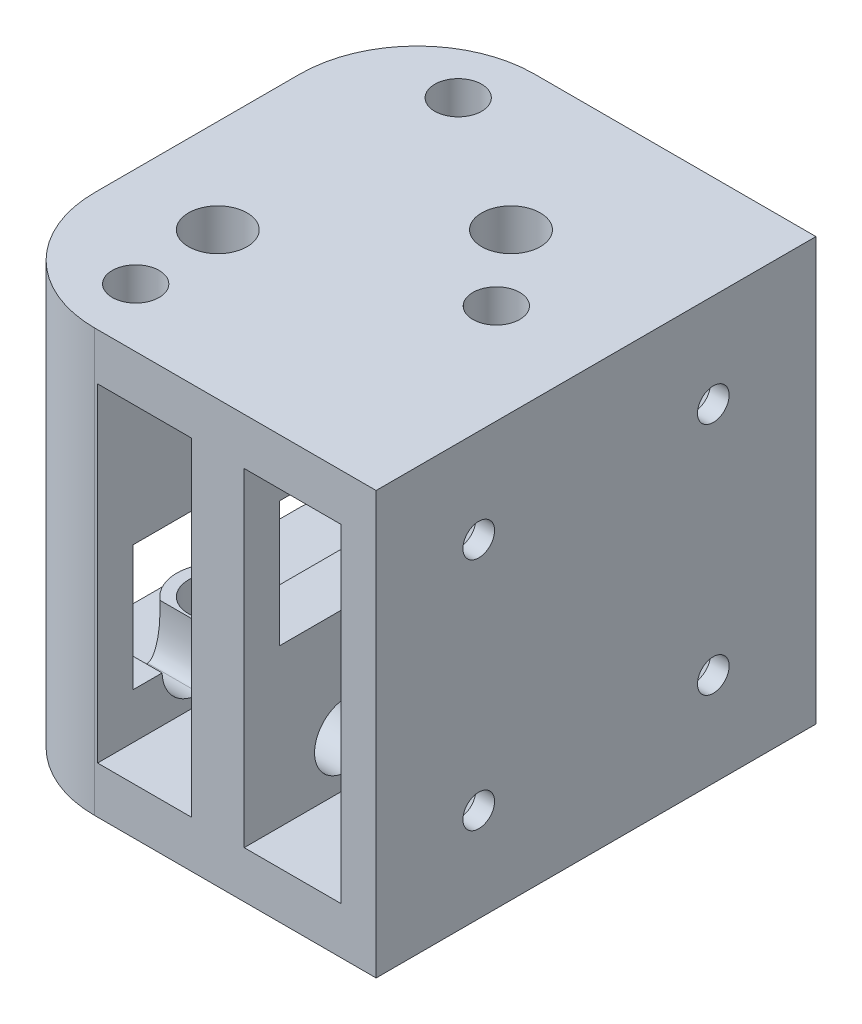
SolidWorks part; units mm, degrees
ref_plane "Front Plane" through (0, 0, 0) normal (0, 0, 1) x (1, 0, 0)
ref_plane "Top Plane" through (0, 0, 0) normal (0, 1, 0) x (1, 0, 0)
ref_plane "Right Plane" through (0, 0, 0) normal (1, 0, 0) x (0, 0, -1)
sketch "Top-Sketch1" plane through (0, 0, 0) normal (0, 1, 0) x (1, 0, 0)
  line L1 (0, 0) -> (34, 0)
  line L2 (0, 0) -> (0, 37.5)
  line L3 (0, 37.5) -> (34, 37.5)
  line L4 (34, 0) -> (34, 37.5)
  circle A0 centre (8.5, 32.5) radius 2
  circle A1 centre (8.5, 5) radius 2
  circle A2 centre (8, 12.5) radius 2.5
  circle A3 centre (20.5, 25) radius 2.5
  dimension "D3" = 5
  dimension "D5" = 4
  dimension "D1" = 13.5
  dimension "D2" = 12.5
  dimension "D4" = 12.5
  dimension "D6" = 8
  dimension "D8" = 12.5
  dimension "D9" = 5
  dimension "D10" = 5
  dimension "D11" = 37.5
  dimension "D12" = 12.5
  dimension "D7" = 25.5
extrude "Boss-Extrude4" add sketch "Top-Sketch1" along normal blind 4
sketch "TopRightRiser" plane through (0, 0, 0) normal (0, -1, 0) x (1, 0, 0)
  line L0 (5.75, -9.819) -> (5.75, 0)
  line L1 (0, 0) -> (34, 0) construction
  line L2 (5.75, 0) -> (10.25, 0)
  line L3 (10.25, 0) -> (10.25, -9.819)
  arc A0 (5.75, -9.819) -> (10.25, -9.819) centre (8, -12.5) ccw
  circle A1 centre (8, -12.5) radius 2.5 construction
  circle A2 centre (8, -12.5) radius 2.5
  point P13 (8, 0)
  dimension "D1" = 7
  dimension "D2" = 4.5
extrude "TopRightRiserBoss-Extrude5" add sketch "TopRightRiser" along normal blind 14.4
sketch "TopLeft" plane through (0, 0, 0) normal (0, -1, 0) x (1, 0, 0)
  line L0 (18.25, -22.319) -> (18.25, 0)
  line L1 (10.25, 0) -> (34, 0) construction
  line L2 (18.25, 0) -> (22.75, 0)
  line L3 (22.75, 0) -> (22.75, -22.319)
  line L4 (10.25, 0) -> (5.75, 0) construction
  circle A0 centre (20.5, -25) radius 2.5
  circle A1 centre (20.5, -25) radius 2.5 construction
  arc A2 (18.25, -22.319) -> (22.75, -22.319) centre (20.5, -25) ccw
  arc A3 (5.75, -9.819) -> (10.25, -9.819) centre (8, -12.5) ccw construction
  point P16 (20.5, 0)
extrude "TopLeftBoss-Extrude6" add sketch "TopLeft" along normal blind 4.9
sketch "MidWall" plane through (0, 0, 0) normal (0, -1, 0) x (-1, 0, 0)
  line L0 (-10.25, 9.819) -> (-10.25, 5.9682) construction
  line L1 (0, 3) -> (-10.25, 3)
  line L2 (0, 3) -> (0, 0)
  line L3 (0, 0) -> (-10.25, 0)
  line L4 (-10.25, 3) -> (-10.25, 0)
  line L5 (0, 37.5) -> (0, 0) construction
  line L6 (-10.25, 0) -> (-5.75, 0) construction
  line L7 (-18.25, 0) -> (-18.25, 22.319) construction
  line L8 (-18.25, 0) -> (-22.75, 0)
  line L9 (-18.25, 0) -> (-18.25, 3)
  line L10 (-18.25, 3) -> (-22.75, 3)
  line L11 (-22.75, 0) -> (-22.75, 3)
  line L12 (-22.75, 22.319) -> (-22.75, 0) construction
  line L13 (-10.25, 0) -> (-18.25, 0) construction
  line L14 (-22.75, 0) -> (-34, 0) construction
  line L15 (-31, 0) -> (-34, 0)
  line L16 (-31, 0) -> (-31, 37.5)
  line L17 (-31, 37.5) -> (-34, 37.5)
  line L18 (-34, 0) -> (-34, 37.5)
  line L19 (-34, 37.5) -> (0, 37.5) construction
  line L20 (-34, 0) -> (-34, 37.5) construction
  dimension "D1" = 3
extrude "MidWallBoss-Extrude7" add sketch "MidWall" along normal blind 28
sketch "Bottom" plane through (0, -28, 0) normal (0, -1, 0) x (1, 0, 0)
  line L0 (0, 0) -> (34, 0) construction
  line L1 (0, 0) -> (34, 0)
  line L2 (0, 0) -> (0, -37.5)
  line L3 (0, -37.5) -> (34, -37.5)
  line L4 (34, 0) -> (34, -37.5)
  line L5 (34, 0) -> (34, -37.5) construction
  line L6 (0, -37.5) -> (0, 0) construction
extrude "BottomBoss-Extrude8" add sketch "Bottom" along normal blind 4
sketch "LowerRight" plane through (0, -28, 0) normal (0, 1, 0) x (1, 0, 0)
  line L0 (5.75, 9.819) -> (5.75, 3)
  line L1 (5.75, 3) -> (10.25, 3)
  line L2 (10.25, 3) -> (10.25, 9.819)
  line L6 (10.25, 9.819) -> (10.25, 3) construction
  line L7 (5.75, 3) -> (5.75, 9.819) construction
  line L8 (10.25, 3) -> (5.75, 3) construction
  circle A0 centre (8, 12.5) radius 2.5
  arc A1 (10.25, 9.819) -> (5.75, 9.819) centre (8, 12.5) ccw
  circle A2 centre (8, 12.5) radius 2.5 construction
  arc A3 (10.25, 9.819) -> (5.75, 9.819) centre (8, 12.5) ccw construction
extrude "LowerRightBoss-Extrude10" add sketch "LowerRight" along normal blind 4.9
sketch "LowerLeft" plane through (0, -28, 0) normal (0, 1, 0) x (1, 0, 0)
  line L1 (18.25, 0) -> (22.75, 0)
  line L5 (0, 0) -> (34, 0) construction
  line L6 (18.25, 22.319) -> (18.25, 0)
  line L7 (22.75, 22.319) -> (22.75, 0)
  circle A0 centre (20.5, 25) radius 2.5
  arc A1 (22.75, 22.319) -> (18.25, 22.319) centre (20.5, 25) ccw
  circle A2 centre (20.5, 25) radius 2.5 construction
  arc A3 (22.75, 22.319) -> (18.25, 22.319) centre (20.5, 25) ccw construction
  point P3 (20.5, 0)
  dimension "D1" = 4.5
extrude "LowerLeftBoss-Extrude9" add sketch "LowerLeft" along normal blind 14.4
fillet "Fillet1" radius 10 3 edges at (0, -14, 0) (0, -30, -37.5) (0, 2, -37.5)
sketch "LinearRailMountingHoles-Sketch10" plane through (34, 0, 0) normal (1, 0, 0) x (0, 0, -1)
  line L0 (0, 4) -> (37.5, 4) construction
  line L1 (37.5, 4) -> (37.5, -32) construction
  line L3 (37.5, -32) -> (0, -32) construction
  line L4 (0, 4) -> (0, -32) construction
  circle A0 centre (8.75, -4) radius 1
  circle A1 centre (8.75, -24) radius 1
  circle A2 centre (28.75, -24) radius 1
  circle A3 centre (28.75, -4) radius 1
  dimension "D7" = 2
  dimension "D1" = 8
  dimension "D2" = 20
  dimension "D3" = 20
  dimension "D4" = 8.75
  dimension "D5" = 8
  dimension "D6" = 8.75
extrude "LinearRailMountingHolesCut-Extrude1" cut sketch "LinearRailMountingHoles-Sketch10" against normal blind 3
sketch "TopRightInset-Sketch1" plane through (0, -14.4, 0) normal (0, -1, 0) x (1, 0, 0)
  line L0 (5.75, -9.819) -> (5.75, -3)
  line L1 (5.75, -3) -> (10.25, -3)
  line L2 (10.25, -3) -> (10.25, -9.819)
  line L3 (5.75, -9.819) -> (5.75, -3) construction
  line L4 (5.75, -3) -> (10.25, -3) construction
  line L5 (10.25, -3) -> (10.25, -9.819) construction
  arc A0 (10.25, -9.819) -> (5.75, -9.819) centre (8, -12.5) ccw
  arc A1 (5.75, -9.819) -> (10.25, -9.819) centre (8, -12.5) ccw construction
extrude "TopRightInset-Cut-Extrude1" cut sketch "TopRightInset-Sketch1" against normal blind 1
sketch "TopLeftInset-Sketch2" plane through (0, -4.9, 0) normal (0, -1, 0) x (1, 0, 0)
  line L0 (18.25, -22.319) -> (18.25, -3)
  line L1 (18.25, -3) -> (22.75, -3)
  line L2 (22.75, -3) -> (22.75, -22.319)
  line L3 (22.75, -3) -> (18.25, -3) construction
  line L4 (22.75, -22.319) -> (22.75, -3) construction
  line L5 (18.25, -22.319) -> (18.25, -3) construction
  arc A0 (22.75, -22.319) -> (18.25, -22.319) centre (20.5, -25) ccw
  arc A1 (18.25, -22.319) -> (22.75, -22.319) centre (20.5, -25) ccw construction
extrude "TopLeftInset-Cut-Extrude2" cut sketch "TopLeftInset-Sketch2" against normal blind 1
sketch "LowerLeftInset-Sketch3" plane through (0, -13.6, 0) normal (0, 1, 0) x (1, 0, 0)
  line L0 (18.25, 22.319) -> (18.25, 3)
  line L1 (18.25, 3) -> (22.75, 3)
  line L2 (22.75, 3) -> (22.75, 22.319)
  line L3 (22.75, 3) -> (18.25, 3) construction
  line L4 (18.25, 22.319) -> (18.25, 3) construction
  line L5 (22.75, 3) -> (22.75, 22.319) construction
  arc A0 (18.25, 22.319) -> (22.75, 22.319) centre (20.5, 25) ccw
  arc A1 (22.75, 22.319) -> (18.25, 22.319) centre (20.5, 25) ccw construction
extrude "LowerLeftInset-Cut-Extrude3" cut sketch "LowerLeftInset-Sketch3" against normal blind 1
sketch "LowerRightInset-Sketch4" plane through (0, -23.1, 0) normal (0, 1, 0) x (1, 0, 0)
  line L0 (5.75, 9.819) -> (5.75, 3)
  line L1 (5.75, 3) -> (10.25, 3)
  line L2 (10.25, 3) -> (10.25, 9.819)
  line L3 (10.25, 3) -> (5.75, 3) construction
  line L4 (5.75, 3) -> (5.75, 9.819) construction
  line L5 (10.25, 9.819) -> (10.25, 3) construction
  arc A0 (5.75, 9.819) -> (10.25, 9.819) centre (8, 12.5) ccw
  arc A1 (10.25, 9.819) -> (5.75, 9.819) centre (8, 12.5) ccw construction
extrude "LowerRightInsetCut-Extrude4" cut sketch "LowerRightInset-Sketch4" against normal blind 1
sketch "PushPinHoleSketch1" plane through (0, -32, 0) normal (0, -1, 0) x (1, 0, 0)
  circle A0 centre (20.5, -25) radius 1
  circle A1 centre (8, -12.5) radius 1
  circle A2 centre (8, -12.5) radius 2.5 construction
  circle A3 centre (20.5, -25) radius 2.5 construction
  dimension "D1" = 2
extrude "PushPinHoleCut-Extrude5" cut sketch "PushPinHoleSketch1" against normal through all
sketch "TopRightMountHoleAccessSketch2" plane through (5.75, 0, 0) normal (-1, 0, 0) x (0, 0, 1)
  circle A0 centre (-8.75, -4) radius 2.75
  dimension "D1" = 5.5
extrude "TopRightMountHoleAccessCut-Extrude2" cut sketch "TopRightMountHoleAccessSketch2" against normal blind 20 and the other way through all
sketch "BottomRightMountHoleAccessSketch3" plane through (18.25, 0, 0) normal (-1, 0, 0) x (0, 0, 1)
  circle A0 centre (-8.75, -24) radius 2.75
  dimension "D1" = 5.5
extrude "BottomRightMountHoleAccessCut-Extrude3" cut sketch "BottomRightMountHoleAccessSketch3" against normal blind 5
sketch "Sketch6" plane through (31, 0, 0) normal (-1, 0, 0) x (0, 0, 1)
  point P0 (-28.75, -4)
  point P3 (-8.75, -4)
  point P6 (-8.75, -24)
  point P9 (-28.75, -24)
hole_wizard "CSK for M2.5 Flat Head Machine Screw1" positions "Sketch6" profile "Sketch7" countersink size "M2.5" standard "ANSI Metric" end condition through all
sketch "Sketch7" plane through (31, -4, -28.75) normal (0, 1, 0) x (0, 0, 1)
  line L0 (0, 0) -> (0, 3)
  line L1 (0, 3) -> (1.35, 3)
  line L2 (1.35, 3) -> (1.35, 1.4)
  line L3 (1.35, 1.4) -> (2.75, 0)
  line L5 (2.75, 0) -> (0, 0)
  line L6 (-1.35, 1.4) -> (-2.75, 0) construction
  line L11 (0, -6.35) -> (0, 107.95) construction
  dimension "Thru Hole Dia." = 2.7
  dimension "Thru Hole Depth" = 3
  dimension "Near C'Sink Dia." = 5.5
  dimension "Near C'Sink Angle" = 90
sketch "BottomRightElipseMountHoleSketch8" plane through (5.75, 0, 0) normal (-1, 0, 0) x (0, 0, 1)
  arc A2 (-8.75, -27.2517) -> (-8.75, -20.7483) centre (-8.75, -24) ccw
  ellipse E0 centre (-8.75, -24) end of major axis (-8.75, -20.7483) minor radius 1.0675 (-8.75, -20.7483) -> (-8.75, -27.2517) ccw
extrude "BottomRightElipseMountHoleCut-Extrude1" cut sketch "BottomRightElipseMountHoleSketch8" against normal blind 10
sketch "TopBackClampHoleSketch8" plane through (0, 4, 0) normal (0, 1, 0) x (1, 0, 0)
  line L0 (34, 0) -> (34, 37.5) construction
  line L1 (34, 37.5) -> (10, 37.5) construction
  circle A0 centre (25.5, 18.75) radius 2
  circle A1 centre (8.5, 5) radius 2 construction
  dimension "D1" = 8.5
  dimension "D2" = 18.75
extrude "TopBackClampHoleCut-Extrude1" cut sketch "TopBackClampHoleSketch8" against normal blind 4
equation "\"GABDepth\"= \"GABDistanceFromBackToFirstPulley\" + \"GABPulleyDDistanceBetween\" + \"GABDistanceFromPulleyToFront\""
equation "\"GABWidth\"= \"StandardWallThickness\" + \"GABDistanceFromLSideToPulley\" + \"GABPulleyWDistanceBetween\" + \"GABDistanceFromPulleyToRSide\""
equation "\"GABLowerHeight\"= 4mm"
equation "\"GABUpperHeight\"= 4mm"
equation "\"GABMidWallHeight\"= 28mm'Must equal 28 or changes alignment"
equation "\"StandardWallThickness\"= 3mm"
equation "\"GABMidShortRiserHeight\"= \"GABMidWallHeight\" / 2 - \"20TGT2PulleyWidth\"'Equals 5.3"
equation "\"LinearGBMountHolesXDistance\"= 20mm'Spec"
equation "\"GABHeight\"= \"GABLowerHeight\" + \"GABMidWallHeight\" + \"GABUpperHeight\""
equation "\"GBMountingHoleDiameter\"= 2mm"
equation "\"GABMidLongRiserHeight\"= \"GABMidWallHeight\" - \"GABMidShortRiserHeight\" - \"20TGT2PulleyWidth\"'Equals 14"
equation "\"GABLRClampHoleOffsetFromSide\"= 5mm"
equation "\"GABDistanceFromBackToFirstPulley\"= 13.5mm"
equation "\"GABPulleyDDistanceBetween\"= 12.5mm'From the100"
equation "\"GABPulleyWDistanceBetween\"= 14.5mm'From the100"
equation "\"GABDistanceFromPulleyToFront\"= 8mm"
equation "\"GABDistanceFromLSideToPulley\"= 9.5mm + \"StandardWallThickness\""
equation "\"GABDistanceFromPulleyToRSide\"= 7.5mm"
equation "\"GABDistanceToFrontRearClampHoles\"= 8.5mm"
equation "\"SteelShaft5mmHoleDiameter\"= 5mm"
equation "\"20TGT2PulleyWidth\"= 8.7mm'The STL of the Pulley in the diagram is a bit larger"
equation "\"7mmx1mmSpacerDiameter\"= 7mm"
equation "\"7mmx1mmSpacerHeight\"= 1mm"
equation "\"GABRiserBossOffset\"= 0.4mm'Aligns Pulleys inside edges to be 2.5mm (.5mm apart top to bottom)"
equation "\"D1@Top-Sketch1\" = \"GABDistanceFromBackToFirstPulley\""
equation "\"D2@Top-Sketch1\" = \"GABPulleyDDistanceBetween\""
equation "\"D3@Top-Sketch1\" = \"SteelShaft5mmHoleDiameter\""
equation "\"D4@Top-Sketch1\" = \"GABPulleyDDistanceBetween\""
equation "\"D6@Top-Sketch1\" = \"GABDistanceFromPulleyToFront\""
equation "\"D8@Top-Sketch1\" = \"GABDistanceFromLSideToPulley\""
equation "\"D9@Top-Sketch1\" = \"GABLRClampHoleOffsetFromSide\""
equation "\"D10@Top-Sketch1\" = \"GABLRClampHoleOffsetFromSide\""
equation "\"D11@Top-Sketch1\" = \"GABWidth\""
equation "\"D1@Boss-Extrude4\"=\"GABUpperHeight\""
equation "\"D1@TopRightRiserBoss-Extrude5\" = \"GABMidLongRiserHeight\" + \"GABRiserBossOffset\""
equation "\"D1@TopLeftBoss-Extrude6\" = \"GABMidShortRiserHeight\" - \"GABRiserBossOffset\""
equation "\"D1@MidWall\" = \"StandardWallThickness\""
equation "\"D1@MidWallBoss-Extrude7\" = \"GABMidWallHeight\""
equation "\"D1@BottomBoss-Extrude8\" = \"GABLowerHeight\""
equation "\"D1@LowerLeftBoss-Extrude9\" = \"GABMidLongRiserHeight\" + \"GABRiserBossOffset\""
equation "\"D1@LowerRightBoss-Extrude10\" = \"GABMidShortRiserHeight\" - \"GABRiserBossOffset\""
equation "\"D1@LinearRailMountingHoles-Sketch10\" =  ( \"GABHeight\" - \"LinearGBMountHolesXDistance\" )  / 2"
equation "\"D2@LinearRailMountingHoles-Sketch10\"=\"LinearGBMountHolesYDistance\""
equation "\"D3@LinearRailMountingHoles-Sketch10\" = \"LinearGBMountHolesXDistance\""
equation "\"D4@LinearRailMountingHoles-Sketch10\" =  ( \"GABWidth\" - \"LinearGBMountHolesXDistance\" )  / 2"
equation "\"D7@LinearRailMountingHoles-Sketch10\" = \"GBMountingHoleDiameter\""
equation "\"D1@LinearRailMountingHolesCut-Extrude1\" = \"StandardWallThickness\""
equation "\"D1@TopRightInset-Cut-Extrude1\" = \"7mmx1mmSpacerHeight\""
equation "\"D1@TopLeftInset-Cut-Extrude2\" = \"7mmx1mmSpacerHeight\""
equation "\"D1@LowerRightInsetCut-Extrude4\" = \"7mmx1mmSpacerHeight\""
equation "\"D1@TopRightRiser\"=\"7mmx1mmSpacerDiameter\""
equation "\"D7@Top-Sketch1\"=\"GABDepth\" - \"GABDistanceToFrontRearClampHoles\""
equation "\"LinearGBMountHolesYDistance\"= 20mm'Spec"
equation "\"D1@PushPinHoleSketch1\" = \"StealPinPushHoleDiameter\""
equation "\"StealPinPushHoleDiameter\"= 2mm"
equation "\"M3HeatInsertHoleDiameter\"= 4mm'Spec"
equation "\"D5@Top-Sketch1\"=\"M3HeatInsertHoleDiameter\""
equation "\"D1@TopBackClampHoleSketch8\" = \"GABDistanceToFrontRearClampHoles\""
equation "\"D2@TopBackClampHoleSketch8\" = \"GABWidth\" / 2"
equation "\"D1@TopBackClampHoleCut-Extrude1\" = \"GABUpperHeight\""
